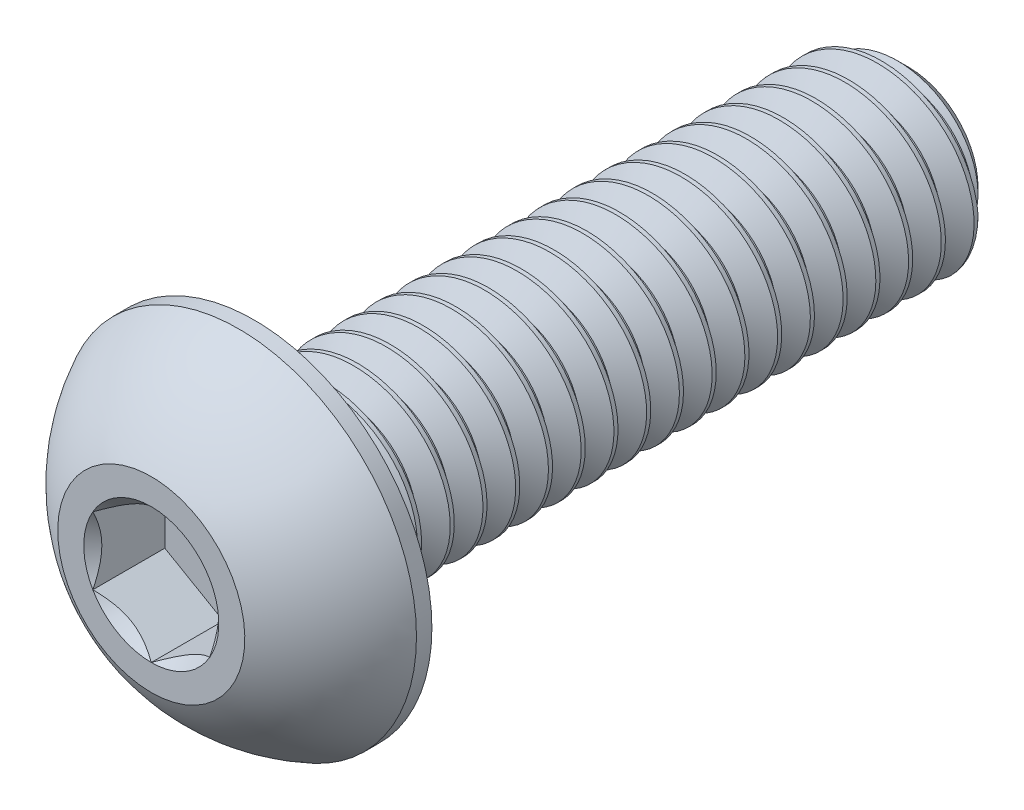
SolidWorks part; units mm, degrees
ref_plane "Front" through (0, 0, 0) normal (0, 0, 1) x (1, 0, 0)
ref_plane "Top" through (0, 0, 0) normal (0, 1, 0) x (1, 0, 0)
ref_plane "Right" through (0, 0, 0) normal (1, 0, 0) x (0, 0, -1)
sketch "Sketch1" plane through (0, 0, 0) normal (1, 0, 0) x (0, 0, -1)
  line L2 (2.2, 2) -> (16.2, 2)
  line L3 (16.2, 2) -> (16.2, 0)
  line L4 (16.2, 0) -> (2.2, 0)
  line L6 (1.87, 3.8) -> (2.2, 3.8) construction
  line L7 (16.2, 2) -> (16.2, -2) construction
  line L8 (0, 0) -> (2.2, 0) construction
  line L9 (2.2, 3.8) -> (2.2, -3.8) construction
  line L11 (2.2, 2) -> (2.2, 0)
  line L13 (0, 1.25) -> (0, -1.25) construction
  line L14 (0, 1.25) -> (0, 2) construction
  arc A3 (0, 2) -> (1.87, 3.8) centre (3.7264, 0) cw construction
  dimension "D1" = 0.33
  dimension "Head Ht" = 2.2
  dimension "Head Dia" = 7.6
  dimension "Dia" = 4
  dimension "Lg" = 14
  dimension "Hex" = 2.5
revolve "Revolve1" add sketch "Sketch1" angle 360 mid plane about L4
sketch "Sketch3" plane through (0, 0, -16.2) normal (0, 0, -1) x (-1, 0, 0)
  circle A0 centre (0, 0) radius 2
curve "Helix/Spiral1" pitch 0.7 height 14.7 radius 2 centre (0, 0, -16.2) axis (0, 0, 1) start towards (0, 1, 0)
sketch "Sketch2" plane through (0, 0, 0) normal (1, 0, 0) x (0, 0, -1)
  line L0 (16.2, 2) -> (16.8125, 2)
  line L1 (16.8125, 2) -> (16.55, 1.5453)
  line L2 (16.55, 1.5453) -> (16.4625, 1.5453)
  line L3 (16.4625, 1.5453) -> (16.2, 2)
  line L4 (16.3312, 1.7727) -> (16.6812, 1.7727) construction
  dimension "D1" = 60
  dimension "D2" = 0.0875
  dimension "D3" = 0.35
chamfer "Chamfer1" distance 0.525 angle 45 1 edges at (0, 2, -16.2)
sweep "Cut-Sweep1" cut profiles "Sketch2" path "Helix/Spiral1" align with end faces yes
sketch "Sketch7" plane through (0, 0, 0) normal (1, 0, 0) x (0, 0, -1)
  line L6 (1.87, 3.8) -> (2.2, 3.8) construction
  line L8 (0, 0) -> (2.2, 0) construction
  line L11 (2.2, 3.8) -> (2.2, -3.8) construction
  line L12 (1.87, 3.8) -> (2.2, 3.8)
  line L13 (0, 0) -> (2.2, 0)
  line L14 (0, 1.25) -> (0, -1.25) construction
  line L15 (2.2, 3.8) -> (2.2, 0)
  line L16 (0, 2) -> (0, 0)
  arc A2 (1.87, 3.8) -> (0, 2) centre (3.7264, 0) ccw construction
  arc A3 (1.87, 3.8) -> (0, 2) centre (3.7264, 0) ccw
revolve "Revolve2" add sketch "Sketch7" angle 360 mid plane about L13
sketch "Sketch5" plane through (0, 0, 0) normal (0, 0, 1) x (1, 0, 0)
  line L1 (1.25, -0.7217) -> (1.25, 0.7217)
  line L2 (1.25, 0.7217) -> (0, 1.4434)
  line L3 (0, 1.4434) -> (-1.25, 0.7217)
  line L4 (-1.25, 0.7217) -> (-1.25, -0.7217)
  line L5 (-1.25, -0.7217) -> (0, -1.4434)
  line L6 (0, -1.4434) -> (1.25, -0.7217)
  circle A0 centre (0, 0) radius 1.25 construction
extrude "Cut-Extrude2" cut sketch "Sketch5" against normal blind 1.54
sketch "Sketch6" plane through (0, 0, 0) normal (0, 0, 1) x (1, 0, 0)
  circle A0 centre (0, 0) radius 1.4434
extrude "Cut-Extrude3" cut sketch "Sketch6" against normal blind 1.54 draft 45
sketch "Sketch9" [suppressed] plane through (0, 0, -2.2) normal (0, 0, 1) x (1, 0, 0)
  circle A2 centre (0, 0) radius 2
extrude "Boss-Extrude2" [suppressed] add sketch "Sketch9" against normal offset from surface (5 mm away) 28.575 up to face at (0, 1.475, -16.2)
sketch "Sketch10" plane through (0, 0, 0) normal (1, 0, 0) x (0, 0, -1)
  line L0 (16.2, 2) -> (16.2, -2) construction
  point P0 (15.15, -2)
  dimension "D1" = 1.05
equation "\"D3@Helix/Spiral1\" = \"Lg@Sketch1\" + \"D4@Helix/Spiral1\""
equation "\"D2@Sketch2\" = \"D4@Helix/Spiral1\" * .125"
equation "\"D3@Sketch2\" = \"D4@Helix/Spiral1\" * .5"
equation "\"D1@Chamfer1\" = \"D4@Helix/Spiral1\" * .75"
equation "\"D1@Cut-Extrude2\" = \"Head Ht@Sketch1\" * .7"
equation "\"D1@Sketch1\" = \"Head Ht@Sketch1\" * .15"
equation "\"D1@Sketch10\" = \"D4@Helix/Spiral1\" * 1.5"
equation "\"D1@Cut-Extrude3\" = \"D1@Cut-Extrude2\""
